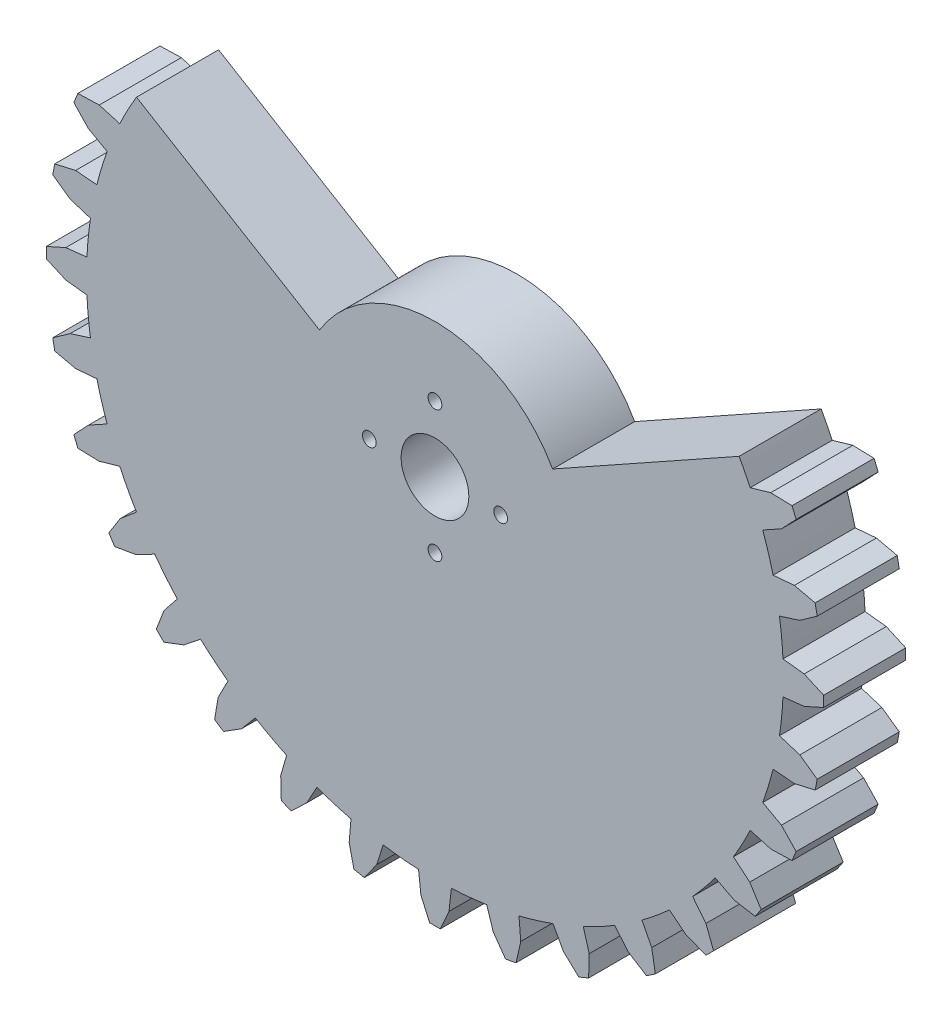
SolidWorks part; units mm, degrees
ref_plane "Plan de face" through (0, 0, 0) normal (0, 0, 1) x (1, 0, 0)
ref_plane "Plan de dessus" through (0, 0, 0) normal (0, 1, 0) x (1, 0, 0)
ref_plane "Plan de droite" through (0, 0, 0) normal (1, 0, 0) x (0, 0, -1)
sketch "Esquisse1" plane through (0, 0, 0) normal (0, 0, 1) x (1, 0, 0)
  line L0 (-2, 42.3979) -> (-1.7102, 44.9817)
  line L1 (0, 2.2889) -> (0, 19223.5431) construction
  line L2 (-1.7102, 44.9817) -> (-0.65, 47.3557)
  line L3 (-0.65, 47.3557) -> (0.65, 47.3557)
  line L4 (-2.3545, 0) -> (49997.6455, 0) construction
  line L5 (2, 42.3979) -> (1.7102, 44.9817)
  line L6 (1.7102, 44.9817) -> (0.65, 47.3557)
  line L7 (6.3098, 41.9734) -> (7.0982, 44.451)
  line L8 (7.0982, 44.451) -> (8.6011, 46.5726)
  line L9 (8.6011, 46.5726) -> (9.8761, 46.3189)
  line L10 (10.4528, 43.7837) -> (9.8761, 46.3189)
  line L11 (10.233, 41.193) -> (10.4528, 43.7837)
  line L12 (14.3772, 39.9359) -> (15.6337, 42.2121)
  line L13 (15.6337, 42.2121) -> (17.5217, 43.9997)
  line L14 (17.5217, 43.9997) -> (18.7228, 43.5022)
  line L15 (18.7937, 40.9032) -> (18.7228, 43.5022)
  line L16 (18.0727, 38.4051) -> (18.7937, 40.9032)
  line L17 (21.892, 36.3637) -> (23.5685, 38.351)
  line L18 (23.5685, 38.351) -> (25.769, 39.7359)
  line L19 (25.769, 39.7359) -> (26.8499, 39.0137)
  line L20 (26.4124, 36.4508) -> (26.8499, 39.0137)
  line L21 (25.2179, 34.1414) -> (26.4124, 36.4508)
  line L22 (28.5656, 31.394) -> (30.5975, 33.0161)
  line L23 (30.5975, 33.0161) -> (33.0259, 33.9451)
  line L24 (33.0259, 33.9451) -> (33.9451, 33.0259)
  line L25 (33.0161, 30.5975) -> (33.9451, 33.0259)
  line L26 (31.394, 28.5656) -> (33.0161, 30.5975)
  line L27 (34.1414, 25.2179) -> (36.4508, 26.4124)
  line L28 (36.4508, 26.4124) -> (39.0137, 26.8499)
  line L29 (39.0137, 26.8499) -> (39.7359, 25.769)
  line L30 (38.351, 23.5685) -> (39.7359, 25.769)
  line L31 (36.3637, 21.892) -> (38.351, 23.5685)
  line L32 (38.4051, 18.0727) -> (40.9032, 18.7937)
  line L33 (40.9032, 18.7937) -> (43.5022, 18.7228)
  line L34 (43.5022, 18.7228) -> (43.9997, 17.5217)
  line L35 (42.2121, 15.6337) -> (43.9997, 17.5217)
  line L36 (39.9359, 14.3772) -> (42.2121, 15.6337)
  line L37 (41.193, 10.233) -> (43.7837, 10.4528)
  line L38 (43.7837, 10.4528) -> (46.3189, 9.8761)
  line L39 (46.3189, 9.8761) -> (46.5726, 8.6011)
  line L40 (44.451, 7.0982) -> (46.5726, 8.6011)
  line L41 (41.9734, 6.3098) -> (44.451, 7.0982)
  line L42 (42.3979, 2) -> (44.9817, 1.7102)
  line L43 (44.9817, 1.7102) -> (47.3557, 0.65)
  line L44 (47.3557, 0.65) -> (47.3557, -0.65)
  line L45 (44.9817, -1.7102) -> (47.3557, -0.65)
  line L46 (42.3979, -2) -> (44.9817, -1.7102)
  line L47 (41.9734, -6.3098) -> (44.451, -7.0982)
  line L48 (44.451, -7.0982) -> (46.5726, -8.6011)
  line L49 (46.5726, -8.6011) -> (46.3189, -9.8761)
  line L50 (43.7837, -10.4528) -> (46.3189, -9.8761)
  line L51 (41.193, -10.233) -> (43.7837, -10.4528)
  line L52 (39.9359, -14.3772) -> (42.2121, -15.6337)
  line L53 (42.2121, -15.6337) -> (43.9997, -17.5217)
  line L54 (43.9997, -17.5217) -> (43.5022, -18.7228)
  line L55 (40.9032, -18.7937) -> (43.5022, -18.7228)
  line L56 (38.4051, -18.0727) -> (40.9032, -18.7937)
  line L57 (36.3637, -21.892) -> (38.351, -23.5685)
  line L58 (38.351, -23.5685) -> (39.7359, -25.769)
  line L59 (39.7359, -25.769) -> (39.0137, -26.8499)
  line L60 (36.4508, -26.4124) -> (39.0137, -26.8499)
  line L61 (34.1414, -25.2179) -> (36.4508, -26.4124)
  line L62 (31.394, -28.5656) -> (33.0161, -30.5975)
  line L63 (33.0161, -30.5975) -> (33.9451, -33.0259)
  line L64 (33.9451, -33.0259) -> (33.0259, -33.9451)
  line L65 (30.5975, -33.0161) -> (33.0259, -33.9451)
  line L66 (28.5656, -31.394) -> (30.5975, -33.0161)
  line L67 (25.2179, -34.1414) -> (26.4124, -36.4508)
  line L68 (26.4124, -36.4508) -> (26.8499, -39.0137)
  line L69 (26.8499, -39.0137) -> (25.769, -39.7359)
  line L70 (23.5685, -38.351) -> (25.769, -39.7359)
  line L71 (21.892, -36.3637) -> (23.5685, -38.351)
  line L72 (18.0727, -38.4051) -> (18.7937, -40.9032)
  line L73 (18.7937, -40.9032) -> (18.7228, -43.5022)
  line L74 (18.7228, -43.5022) -> (17.5217, -43.9997)
  line L75 (15.6337, -42.2121) -> (17.5217, -43.9997)
  line L76 (14.3772, -39.9359) -> (15.6337, -42.2121)
  line L77 (10.233, -41.193) -> (10.4528, -43.7837)
  line L78 (10.4528, -43.7837) -> (9.8761, -46.3189)
  line L79 (9.8761, -46.3189) -> (8.6011, -46.5726)
  line L80 (7.0982, -44.451) -> (8.6011, -46.5726)
  line L81 (6.3098, -41.9734) -> (7.0982, -44.451)
  line L82 (2, -42.3979) -> (1.7102, -44.9817)
  line L83 (1.7102, -44.9817) -> (0.65, -47.3557)
  line L84 (0.65, -47.3557) -> (-0.65, -47.3557)
  line L85 (-1.7102, -44.9817) -> (-0.65, -47.3557)
  line L86 (-2, -42.3979) -> (-1.7102, -44.9817)
  line L87 (-6.3098, -41.9734) -> (-7.0982, -44.451)
  line L88 (-7.0982, -44.451) -> (-8.6011, -46.5726)
  line L89 (-8.6011, -46.5726) -> (-9.8761, -46.3189)
  line L90 (-10.4528, -43.7837) -> (-9.8761, -46.3189)
  line L91 (-10.233, -41.193) -> (-10.4528, -43.7837)
  line L92 (-14.3772, -39.9359) -> (-15.6337, -42.2121)
  line L93 (-15.6337, -42.2121) -> (-17.5217, -43.9997)
  line L94 (-17.5217, -43.9997) -> (-18.7228, -43.5022)
  line L95 (-18.7937, -40.9032) -> (-18.7228, -43.5022)
  line L96 (-18.0727, -38.4051) -> (-18.7937, -40.9032)
  line L97 (-21.892, -36.3637) -> (-23.5685, -38.351)
  line L98 (-23.5685, -38.351) -> (-25.769, -39.7359)
  line L99 (-25.769, -39.7359) -> (-26.8499, -39.0137)
  line L100 (-26.4124, -36.4508) -> (-26.8499, -39.0137)
  line L101 (-25.2179, -34.1414) -> (-26.4124, -36.4508)
  line L102 (-28.5656, -31.394) -> (-30.5975, -33.0161)
  line L103 (-30.5975, -33.0161) -> (-33.0259, -33.9451)
  line L104 (-33.0259, -33.9451) -> (-33.9451, -33.0259)
  line L105 (-33.0161, -30.5975) -> (-33.9451, -33.0259)
  line L106 (-31.394, -28.5656) -> (-33.0161, -30.5975)
  line L107 (-34.1414, -25.2179) -> (-36.4508, -26.4124)
  line L108 (-36.4508, -26.4124) -> (-39.0137, -26.8499)
  line L109 (-39.0137, -26.8499) -> (-39.7359, -25.769)
  line L110 (-38.351, -23.5685) -> (-39.7359, -25.769)
  line L111 (-36.3637, -21.892) -> (-38.351, -23.5685)
  line L112 (-38.4051, -18.0727) -> (-40.9032, -18.7937)
  line L113 (-40.9032, -18.7937) -> (-43.5022, -18.7228)
  line L114 (-43.5022, -18.7228) -> (-43.9997, -17.5217)
  line L115 (-42.2121, -15.6337) -> (-43.9997, -17.5217)
  line L116 (-39.9359, -14.3772) -> (-42.2121, -15.6337)
  line L117 (-41.193, -10.233) -> (-43.7837, -10.4528)
  line L118 (-43.7837, -10.4528) -> (-46.3189, -9.8761)
  line L119 (-46.3189, -9.8761) -> (-46.5726, -8.6011)
  line L120 (-44.451, -7.0982) -> (-46.5726, -8.6011)
  line L121 (-41.9734, -6.3098) -> (-44.451, -7.0982)
  line L122 (-42.3979, -2) -> (-44.9817, -1.7102)
  line L123 (-44.9817, -1.7102) -> (-47.3557, -0.65)
  line L124 (-47.3557, -0.65) -> (-47.3557, 0.65)
  line L125 (-44.9817, 1.7102) -> (-47.3557, 0.65)
  line L126 (-42.3979, 2) -> (-44.9817, 1.7102)
  line L127 (-41.9734, 6.3098) -> (-44.451, 7.0982)
  line L128 (-44.451, 7.0982) -> (-46.5726, 8.6011)
  line L129 (-46.5726, 8.6011) -> (-46.3189, 9.8761)
  line L130 (-43.7837, 10.4528) -> (-46.3189, 9.8761)
  line L131 (-41.193, 10.233) -> (-43.7837, 10.4528)
  line L132 (-39.9359, 14.3772) -> (-42.2121, 15.6337)
  line L133 (-42.2121, 15.6337) -> (-43.9997, 17.5217)
  line L134 (-43.9997, 17.5217) -> (-43.5022, 18.7228)
  line L135 (-40.9032, 18.7937) -> (-43.5022, 18.7228)
  line L136 (-38.4051, 18.0727) -> (-40.9032, 18.7937)
  line L137 (-36.3637, 21.892) -> (-38.351, 23.5685)
  line L138 (-38.351, 23.5685) -> (-39.7359, 25.769)
  line L139 (-39.7359, 25.769) -> (-39.0137, 26.8499)
  line L140 (-36.4508, 26.4124) -> (-39.0137, 26.8499)
  line L141 (-34.1414, 25.2179) -> (-36.4508, 26.4124)
  line L142 (-31.394, 28.5656) -> (-33.0161, 30.5975)
  line L143 (-33.0161, 30.5975) -> (-33.9451, 33.0259)
  line L144 (-33.9451, 33.0259) -> (-33.0259, 33.9451)
  line L145 (-30.5975, 33.0161) -> (-33.0259, 33.9451)
  line L146 (-28.5656, 31.394) -> (-30.5975, 33.0161)
  line L147 (-25.2179, 34.1414) -> (-26.4124, 36.4508)
  line L148 (-26.4124, 36.4508) -> (-26.8499, 39.0137)
  line L149 (-26.8499, 39.0137) -> (-25.769, 39.7359)
  line L150 (-23.5685, 38.351) -> (-25.769, 39.7359)
  line L151 (-21.892, 36.3637) -> (-23.5685, 38.351)
  line L152 (-18.0727, 38.4051) -> (-18.7937, 40.9032)
  line L153 (-18.7937, 40.9032) -> (-18.7228, 43.5022)
  line L154 (-18.7228, 43.5022) -> (-17.5217, 43.9997)
  line L155 (-15.6337, 42.2121) -> (-17.5217, 43.9997)
  line L156 (-14.3772, 39.9359) -> (-15.6337, 42.2121)
  line L157 (-10.233, 41.193) -> (-10.4528, 43.7837)
  line L158 (-10.4528, 43.7837) -> (-9.8761, 46.3189)
  line L159 (-9.8761, 46.3189) -> (-8.6011, 46.5726)
  line L160 (-7.0982, 44.451) -> (-8.6011, 46.5726)
  line L161 (-6.3098, 41.9734) -> (-7.0982, 44.451)
  arc A17 (6.3098, 41.9734) -> (2, 42.3979) centre (0, 0) ccw
  arc A18 (14.3772, 39.9359) -> (10.233, 41.193) centre (0, 0) ccw
  arc A19 (21.892, 36.3637) -> (18.0727, 38.4051) centre (0, 0) ccw
  arc A20 (28.5656, 31.394) -> (25.2179, 34.1414) centre (0, 0) ccw
  arc A21 (34.1414, 25.2179) -> (31.394, 28.5656) centre (0, 0) ccw
  arc A22 (38.4051, 18.0727) -> (36.3637, 21.892) centre (0, 0) ccw
  arc A23 (41.193, 10.233) -> (39.9359, 14.3772) centre (0, 0) ccw
  arc A24 (42.3979, 2) -> (41.9734, 6.3098) centre (0, 0) ccw
  arc A25 (41.9734, -6.3098) -> (42.3979, -2) centre (0, 0) ccw
  arc A26 (39.9359, -14.3772) -> (41.193, -10.233) centre (0, 0) ccw
  arc A27 (36.3637, -21.892) -> (38.4051, -18.0727) centre (0, 0) ccw
  arc A28 (31.394, -28.5656) -> (34.1414, -25.2179) centre (0, 0) ccw
  arc A29 (25.2179, -34.1414) -> (28.5656, -31.394) centre (0, 0) ccw
  arc A30 (18.0727, -38.4051) -> (21.892, -36.3637) centre (0, 0) ccw
  arc A31 (10.233, -41.193) -> (14.3772, -39.9359) centre (0, 0) ccw
  arc A32 (2, -42.3979) -> (6.3098, -41.9734) centre (0, 0) ccw
  arc A33 (-6.3098, -41.9734) -> (-2, -42.3979) centre (0, 0) ccw
  arc A34 (-14.3772, -39.9359) -> (-10.233, -41.193) centre (0, 0) ccw
  arc A35 (-21.892, -36.3637) -> (-18.0727, -38.4051) centre (0, 0) ccw
  arc A36 (-28.5656, -31.394) -> (-25.2179, -34.1414) centre (0, 0) ccw
  arc A37 (-34.1414, -25.2179) -> (-31.394, -28.5656) centre (0, 0) ccw
  arc A38 (-38.4051, -18.0727) -> (-36.3637, -21.892) centre (0, 0) ccw
  arc A39 (-42.3979, -2) -> (-41.9734, -6.3098) centre (0, 0) ccw
  arc A40 (-41.9734, 6.3098) -> (-42.3979, 2) centre (0, 0) ccw
  arc A41 (-39.9359, 14.3772) -> (-41.193, 10.233) centre (0, 0) ccw
  arc A42 (-36.3637, 21.892) -> (-38.4051, 18.0727) centre (0, 0) ccw
  arc A43 (-31.394, 28.5656) -> (-34.1414, 25.2179) centre (0, 0) ccw
  arc A44 (-25.2179, 34.1414) -> (-28.5656, 31.394) centre (0, 0) ccw
  arc A45 (-18.0727, 38.4051) -> (-21.892, 36.3637) centre (0, 0) ccw
  arc A46 (-10.233, 41.193) -> (-14.3772, 39.9359) centre (0, 0) ccw
  arc A47 (-2, 42.3979) -> (-6.3098, 41.9734) centre (0, 0) ccw
  arc A48 (-41.193, -10.233) -> (-39.9359, -14.3772) centre (0, 0) ccw
  point P17 (0, 47.3557)
  point P83 (0, 0)
  point P204 (0, 0)
  dimension "D1" = 84.89
  dimension "D2" = 32
  dimension "D3" = 2.6
  dimension "D4" = 83.6
  dimension "D5" = 2
  dimension "D6" = 2.6
  dimension "D7" = 0.65
extrude "Boss.-Extru.1" add sketch "Esquisse1" along normal blind 10
sketch "Esquisse2" plane through (0, 0, 10) normal (0, 0, 1) x (1, 0, 0)
  circle A3 centre (0, 0) radius 8 construction
  circle A4 centre (0, 8) radius 0.8387
  circle A5 centre (0, 0) radius 4.125
  circle A6 centre (8, 0) radius 0.8387
  circle A7 centre (0, -8) radius 0.8387
  circle A8 centre (-8, 0) radius 0.8387
  point P16 (0, 0)
  dimension "D1" = 16
  dimension "D2" = 1.6774
  dimension "D3" = 8.25
  dimension "D4" = 4
extrude "Enlèv. mat.-Extru.3" cut sketch "Esquisse2" against normal up to surface (10 mm away) up to face at (0, 0, 0)
sketch "Esquisse3" plane through (0, 0, 10) normal (0, 0, 1) x (1, 0, 0)
  line L0 (37.0515, 20.7066) -> (0, 0) construction
  line L1 (0, 0) -> (-36.3637, 21.892) construction
  line L2 (-36.3637, 21.892) -> (-14.0654, 8.4678)
  line L3 (37.0515, 20.7066) -> (14.3315, 8.0093)
  line L4 (-36.3637, 21.892) -> (-44.7714, 26.9538)
  line L5 (37.0515, 20.7066) -> (45.6183, 25.4942)
  arc A0 (37.0515, 20.7066) -> (-36.3637, 21.892) centre (0, 0) ccw construction
  arc A1 (-2, 42.3979) -> (-6.3098, 41.9734) centre (0, 0) ccw construction
  arc A2 (-14.0654, 8.4678) -> (14.3315, 8.0093) centre (0, 0) cw
  circle A3 centre (0, 0) radius 4.125 construction
  arc A4 (-44.7714, 26.9538) -> (45.6183, 25.4942) centre (0.1388, 8.5967) cw
  point P15 (0, 0)
  point P16 (47.4409, 26.5128)
  point P17 (45.6183, 25.4942)
  point P18 (0, -7.9831)
  point P19 (0, -8)
  point P21 (14.3315, 8.4678)
  point P22 (-44.7714, 26.9538)
  point P23 (-44.7714, 26.9538)
  dimension "D1" = 119.752
extrude "Enlèv. mat.-Extru.6" cut sketch "Esquisse3" against normal up to surface (10 mm away) up to face at (0.8387, 8, 0)
equation "\"L\"= 20cm'Longueur de tensionnement"
